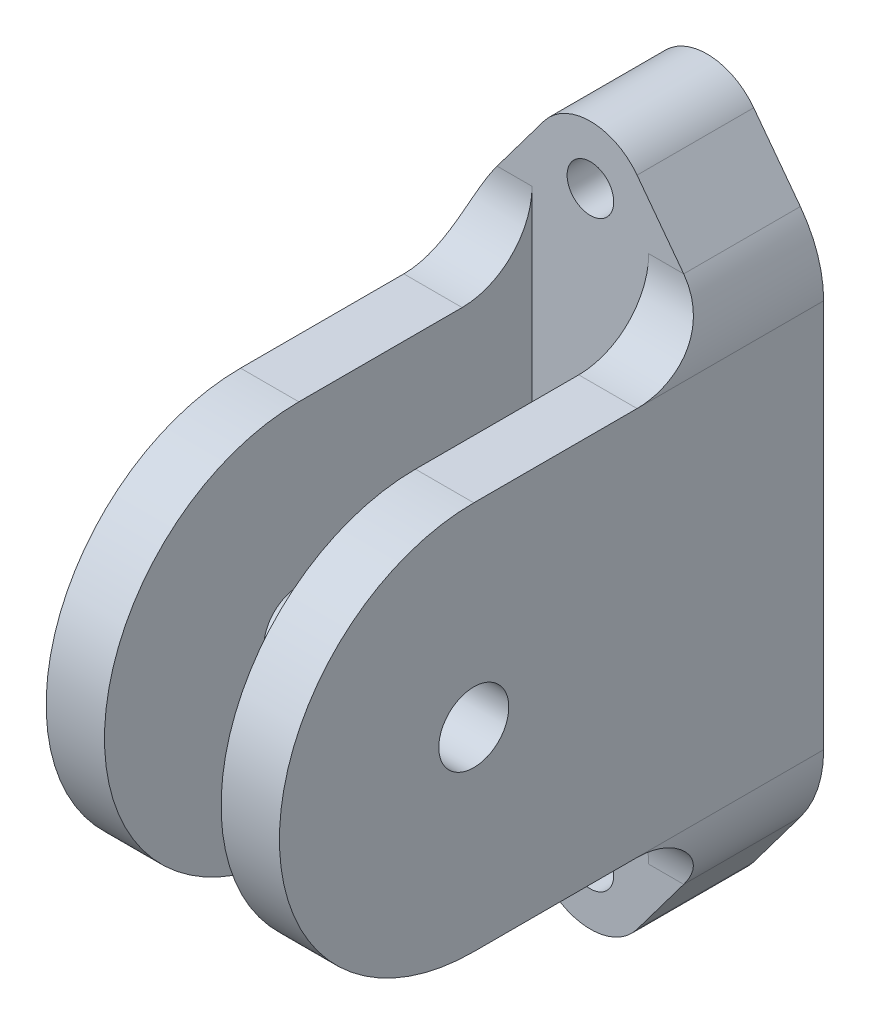
SolidWorks part; units mm, degrees
ref_plane "Plan de face" through (0, 0, 0) normal (0, 0, 1) x (1, 0, 0)
ref_plane "Plan de dessus" through (0, 0, 0) normal (0, 1, 0) x (1, 0, 0)
ref_plane "Plan de droite" through (0, 0, 0) normal (1, 0, 0) x (0, 0, -1)
sketch "Esquisse1" plane through (0, 0, 0) normal (0, 0, 1) x (1, 0, 0)
  line L0 (-4, 11.3333) -> (-2, 14)
  line L1 (-5, 10) -> (5, 10) construction
  line L2 (-5, 8.3333) -> (-5, -8.3333)
  line L3 (-5, -10) -> (5, -10) construction
  line L4 (5, 8.3333) -> (5, -8.3333)
  line L5 (-5, 10) -> (5, -10) construction
  line L6 (-5, -10) -> (5, 10) construction
  line L8 (-5, 0) -> (5, 0) construction
  line L9 (4, -11.3333) -> (2, -14)
  line L10 (-4, -11.3333) -> (-2, -14)
  line L11 (0, -10) -> (0, 12.5) construction
  line L12 (4, 11.3333) -> (2, 14)
  arc A0 (2, 14) -> (-2, 14) centre (0, 12.5) ccw
  circle A1 centre (0, 12.5) radius 1
  arc A2 (2, -14) -> (-2, -14) centre (0, -12.5) cw
  circle A3 centre (0, -12.5) radius 1
  arc A4 (4, -11.3333) -> (5, -8.3333) centre (0, -8.3333) ccw
  arc A5 (-5, -8.3333) -> (-4, -11.3333) centre (0, -8.3333) ccw
  arc A6 (4, 11.3333) -> (5, 8.3333) centre (0, 8.3333) cw
  arc A7 (-4, 11.3333) -> (-5, 8.3333) centre (0, 8.3333) ccw
  point P0 (0, 0)
  dimension "D3" = 5
  dimension "D4" = 2
  dimension "D5" = 2
  dimension "D6" = 5
  dimension "D1" = 10
  dimension "D2" = 20
extrude "Boss.-Extru.1" add sketch "Esquisse1" along normal blind 5
sketch "Esquisse2" plane through (-5, 0, 0) normal (-1, 0, 0) x (0, 0, 1)
  line L0 (5, 8.3333) -> (15, 8.3333)
  line L1 (15, 8.3333) -> (15, -8.3333) construction
  line L2 (15, -8.3333) -> (5, -8.3333)
  line L3 (5, 8.3333) -> (5, -8.3333)
  arc A0 (15, 8.3333) -> (15, -8.3333) centre (15, 0) cw
  circle A1 centre (15, 0) radius 1.5
  dimension "D2" = 3
  dimension "D1" = 10
extrude "Boss.-Extru.2" add sketch "Esquisse2" against normal blind 2.5
mirror "Symétrie1" about plane through (0, 0, 0) normal (1, 0, 0) of "Boss.-Extru.2"
fillet "Congé1" radius 3 4 edges at (3.75, 8.3333, 5) (3.75, -8.3333, 5) (-3.75, 8.3333, 5) (-3.75, -8.3333, 5)
